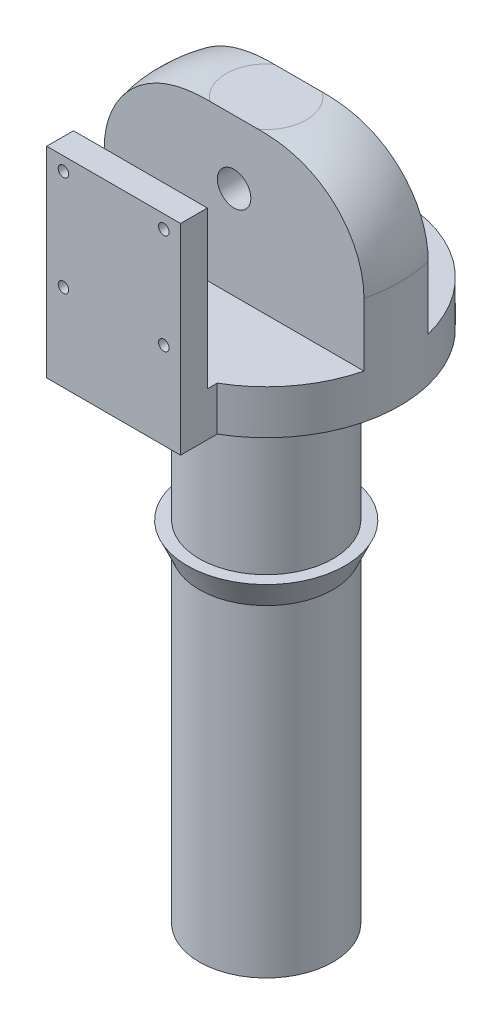
SolidWorks part; units mm, degrees
ref_plane "Front Plane" through (0, 0, 0) normal (0, 0, 1) x (1, 0, 0)
ref_plane "Top Plane" through (0, 0, 0) normal (0, 1, 0) x (1, 0, 0)
ref_plane "Right Plane" through (0, 0, 0) normal (1, 0, 0) x (0, 0, -1)
sketch "Sketch1" plane through (0, 0, 0) normal (0, 1, 0) x (1, 0, 0)
  circle A0 centre (0, 0) radius 12.7
  dimension "D1" = 25.4
extrude "Part that goes into base" add sketch "Sketch1" along normal blind 97.79
sketch "Sketch2" plane through (0, 0, 0) normal (0, 0, 1) x (1, 0, 0)
  line L0 (12.7, 97.79) -> (-12.7, 97.79) construction
  line L1 (12.7, 97.79) -> (-12.7, 97.79)
  line L2 (12.7, 97.79) -> (12.7, 66.294) construction
  line L3 (12.7, 66.294) -> (14.986, 66.294)
  line L4 (14.986, 66.294) -> (12.7, 61.214)
  line L5 (12.7, 61.214) -> (12.7, 66.294)
  line L6 (0, 97.79) -> (0, 52.1662) construction
  dimension "D1" = 31.496
  dimension "D2" = 2.286
  dimension "D3" = 5.08
revolve "Clip in mechanism" add sketch "Sketch2" angle 360 about L6 region at (13.462, 64.6007, 0)
sketch "Sketch3" plane through (0, 97.79, 0) normal (0, 1, 0) x (1, 0, 0)
  circle A0 centre (0, 0) radius 25.4
  dimension "D1" = 50.8
extrude "Top part Extrude" add sketch "Sketch3" along normal blind 38.1
ref_plane "Plane1" through (50.8, 0, 0) normal (1, 0, 0) x (0, 0, -1)
sketch "Sketch4" plane through (50.8, 0, 0) normal (1, 0, 0) x (0, 0, -1)
  line L0 (25.4, 135.89) -> (-25.4, 135.89) construction
  line L1 (25.4, 135.89) -> (-23.876, 135.89)
  line L2 (-12.7, 97.79) -> (12.7, 97.79) construction
  line L8 (6.096, 135.89) -> (6.096, 106.172)
  line L10 (25.4, 97.79) -> (25.4, 135.89) construction
  line L11 (25.4, 106.172) -> (25.4, 135.89)
  line L12 (6.096, 135.89) -> (25.4, 135.89)
  line L13 (25.4, 106.172) -> (6.096, 106.172)
  line L14 (-23.876, 106.172) -> (-6.096, 106.172)
  line L15 (-23.876, 135.89) -> (-6.096, 135.89)
  line L18 (-6.096, 135.89) -> (-6.096, 106.172)
  line L19 (-23.876, 135.89) -> (-23.876, 106.172)
  dimension "D1" = 8.382
  dimension "D3" = 8.382
  dimension "D4" = 19.304
  dimension "D5" = 8.382
  dimension "D6" = 19.304
  dimension "D7" = 1.524
extrude "Cut to Accommodate Encoder" cut sketch "Sketch4" against normal through all
sketch "Sketch5" plane through (0, 106.172, 0) normal (0, 1, 0) x (1, 0, 0)
  line L0 (-13.191, -27.686) -> (15.1785, -27.686)
  line L1 (24.6576, -6.096) -> (24.6576, -40.386)
  line L2 (-24.6576, -6.096) -> (24.6576, -6.096) construction
  line L3 (-24.6576, -6.096) -> (-24.6576, -40.386)
  line L4 (-24.6576, -40.386) -> (24.6576, -40.386)
  arc A0 (24.6576, -6.096) -> (-24.6576, -6.096) centre (0, 0) cw
  dimension "D1" = 21.59
  dimension "D2" = 34.29
sketch "Sketch7" plane through (0, 0, -6.096) normal (0, 0, -1) x (-1, 0, 0)
  line L0 (0, 135.89) -> (0, 123.825) construction
  line L1 (24.6576, 135.89) -> (-24.6576, 135.89) construction
  circle A0 centre (0, 123.825) radius 3.175
  dimension "D2" = 6.35
  dimension "D1" = 12.065
extrude "Bolt Hole" cut sketch "Sketch7" against normal up to surface (12.192 mm away) up to face at (0, 121.031, 6.096)
fillet "Fillet to Accommodate shoulder" radius 17.78 2 edges at (-25.4, 135.89, 0) (25.4, 135.89, 0)
ref_plane "Plane2" through (0, 0, 26.416) normal (0, 0, 1) x (1, 0, 0)
sketch "Sketch11" plane through (0, 135.89, 0) normal (0, 1, 0) x (1, 0, 0)
  line L1 (12.7, -23.876) -> (12.7, -28.956)
  line L2 (12.7, -28.956) -> (-12.7, -28.956)
  line L3 (-12.7, -28.956) -> (-12.7, -23.876)
  line L5 (0, 0) -> (0, -31.0003) construction
  line L8 (-8.6658, -23.876) -> (-12.7, -23.876)
  line L9 (8.6658, -23.876) -> (12.7, -23.876)
  line L10 (-8.6658, -23.876) -> (8.6658, -23.876) construction
  arc A0 (-8.6658, -23.876) -> (8.6658, -23.876) centre (0, 0) ccw
  dimension "D1" = 25.4
  dimension "D2" = 5.08
extrude "Boss-Extrude1" add sketch "Sketch11" against normal up to surface (38.1 mm away) up to face at (0, 97.79, 12.7)
sketch "Sketch12" plane through (0, 106.172, 0) normal (0, 1, 0) x (1, 0, 0)
  line L0 (12.7, -23.876) -> (12.7, -21.997)
  line L1 (-12.7, -23.876) -> (-12.7, -21.997)
  line L2 (-12.7, -23.876) -> (-8.6658, -23.876)
  line L3 (8.6658, -23.876) -> (12.7, -23.876)
  arc A0 (8.6658, -23.876) -> (24.6576, -6.096) centre (0, 0) ccw construction
  arc A1 (-24.6576, -6.096) -> (-8.6658, -23.876) centre (0, 0) ccw construction
  arc A2 (-8.6658, -23.876) -> (-12.7, -21.997) centre (0, 0) cw
  arc A3 (12.7, -21.997) -> (8.6658, -23.876) centre (0, 0) cw
extrude "Boss-Extrude2" add sketch "Sketch12" against normal up to surface (8.382 mm away) up to face at (0, 97.79, 12.7)
sketch "Sketch13" plane through (0, 0, 23.876) normal (0, 0, -1) x (-1, 0, 0)
  line L0 (12.7, 135.89) -> (-12.7, 135.89) construction
  line L1 (0, 135.89) -> (0, 111.6123) construction
  line L2 (-12.7, 123.825) -> (12.3879, 123.825) construction
  line L3 (-12.7, 106.172) -> (-12.7, 135.89) construction
  circle A0 centre (9.525, 133.35) radius 1
  circle A1 centre (-9.525, 133.35) radius 1
  circle A2 centre (-9.525, 114.3) radius 1
  circle A3 centre (9.525, 114.3) radius 1
  circle A4 centre (0, 123.825) radius 3.175 construction
  circle A5 centre (0, 123.825) radius 3.175
  point P20 (0, 0)
  point P21 (0, 0)
  point P22 (0, 0)
  point P23 (0, 0)
  dimension "D1" = 9.525
  dimension "D2" = 9.525
  dimension "D3" = 2.54
  dimension "D4" = 0
extrude "Cut-Extrude1" cut sketch "Sketch13" against normal up to surface (5.08 mm away) contours A2 | A1 | A3 | A0 region at (9.525, 114.3, 23.876) up to face at (0, 116.84, 28.956)
